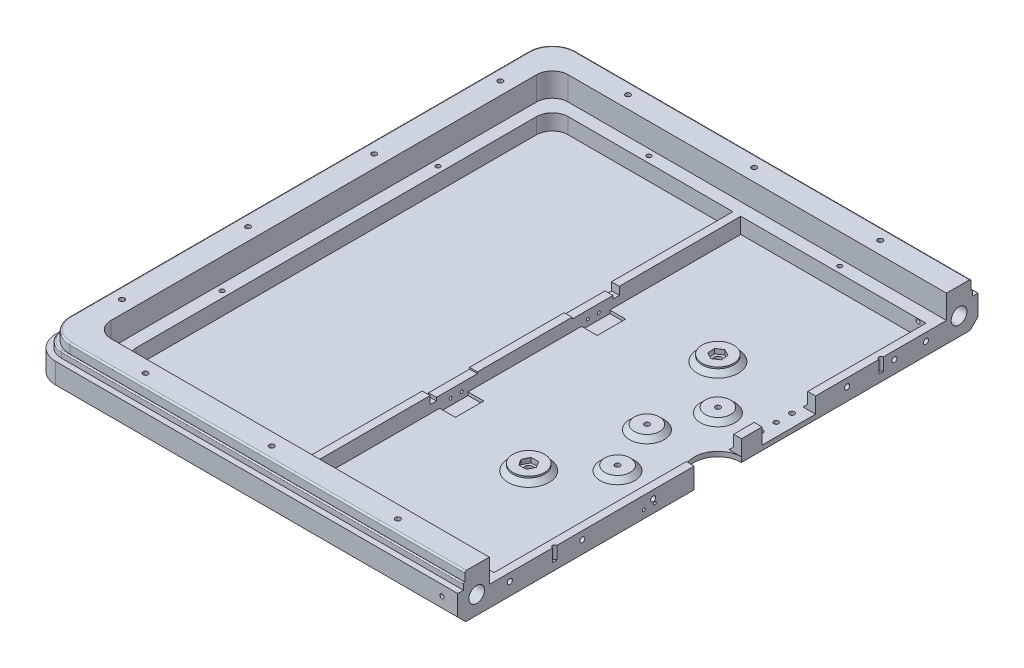
SolidWorks part; units mm, degrees
ref_plane "Front Plane" through (0, 0, 0) normal (0, 0, 1) x (1, 0, 0)
ref_plane "Top Plane" through (0, 0, 0) normal (0, 1, 0) x (1, 0, 0)
ref_plane "Right Plane" through (0, 0, 0) normal (1, 0, 0) x (0, 0, -1)
sketch "Sketch1" plane through (0, 0, 0) normal (0, 1, 0) x (1, 0, 0)
  line L1 (-270, -165) -> (270, -165)
  line L2 (-270, -165) -> (-270, 165)
  line L3 (-270, 165) -> (270, 165)
  line L4 (270, -165) -> (270, 165)
  line L5 (-270, -165) -> (270, 165) construction
  line L6 (-270, 165) -> (270, -165) construction
  point P0 (0, 0)
  dimension "D1" = 540
  dimension "D2" = 330
extrude "Boss-Extrude1" add sketch "Sketch1" along normal blind 3
sketch "Sketch2" plane through (0, 3, 0) normal (0, 1, 0) x (1, 0, 0)
  line L0 (250, 145) -> (-250, 145)
  line L1 (270, -165) -> (-270, -165)
  line L2 (270, -165) -> (270, 165)
  line L3 (270, 165) -> (-270, 165)
  line L4 (-270, -165) -> (-270, 165)
  line L5 (270, -165) -> (-270, 165) construction
  line L6 (270, 165) -> (-270, -165) construction
  line L7 (-250, -145) -> (-250, 145)
  line L8 (250, -145) -> (-250, -145)
  line L9 (250, -145) -> (250, 145)
  point P0 (0, 0)
  dimension "D1" = 20
  dimension "D2" = 540
extrude "Boss-Extrude2" add sketch "Sketch2" along normal blind 25 contours L0 L7 L8 L9 | L2 L1 L4 L3
fillet "Fillet1" radius 15 4 edges at (-270, 14, -165) (-270, 14, 165) (270, 14, 165) (270, 14, -165)
sketch "Sketch4" plane through (0, 28, 0) normal (0, 1, 0) x (1, 0, 0)
  line L0 (-270, 0) -> (-258, 0) construction
  line L1 (-270, -150) -> (-270, 150) construction
  line L2 (-258, 0) -> (-258, 40) construction
  line L3 (-258, 40) -> (-258, 120) construction
  line L4 (0, 0) -> (0, 145) construction
  line L5 (250, 145) -> (-250, 145) construction
  line L6 (0, 165) -> (0, 153) construction
  line L7 (255, 165) -> (-255, 165) construction
  line L8 (0, 153) -> (-50, 153) construction
  line L9 (-50, 153) -> (-130, 153) construction
  line L10 (-130, 153) -> (-210, 153) construction
  line L11 (130, 153) -> (210, 153) construction
  line L12 (50, 153) -> (130, 153) construction
  line L13 (258, 40) -> (258, 120) construction
  line L14 (0, 0) -> (78.1952, 0) construction
  line L15 (258, -40) -> (258, -120) construction
  line L16 (50, -153) -> (130, -153) construction
  line L17 (130, -153) -> (210, -153) construction
  line L18 (-130, -153) -> (-210, -153) construction
  line L19 (-50, -153) -> (-130, -153) construction
  line L20 (0, -153) -> (-50, -153) construction
  line L21 (0, -165) -> (0, -153) construction
  line L22 (-258, -40) -> (-258, -120) construction
  circle A0 centre (-258, 120) radius 1.6
  circle A1 centre (-258, 40) radius 1.6
  circle A2 centre (-210, 153) radius 1.6
  circle A3 centre (-130, 153) radius 1.6
  circle A4 centre (-50, 153) radius 1.6
  circle A5 centre (50, 153) radius 1.6
  circle A6 centre (130, 153) radius 1.6
  circle A7 centre (210, 153) radius 1.6
  circle A8 centre (258, 40) radius 1.6
  circle A9 centre (258, 120) radius 1.6
  circle A10 centre (258, -120) radius 1.6
  circle A11 centre (258, -40) radius 1.6
  circle A12 centre (210, -153) radius 1.6
  circle A13 centre (130, -153) radius 1.6
  circle A14 centre (50, -153) radius 1.6
  circle A15 centre (-50, -153) radius 1.6
  circle A16 centre (-130, -153) radius 1.6
  circle A17 centre (-210, -153) radius 1.6
  circle A18 centre (-258, -40) radius 1.6
  circle A19 centre (-258, -120) radius 1.6
  dimension "D1" = 50
  dimension "D2" = 80
  dimension "D3" = 80
  dimension "D4" = 12
  dimension "D5" = 12
  dimension "D6" = 40
  dimension "D7" = 80
extrude "Cut-Extrude1" cut sketch "Sketch4" against normal up to surface (28 mm away) up to face at (0, 0, 0)
sketch "Sketch5" plane through (0, 3, 0) normal (0, 1, 0) x (1, 0, 0)
  circle A0 centre (0, 0) radius 15
  dimension "D1" = 30
extrude "Cut-Extrude2" cut sketch "Sketch5" against normal up to surface (3 mm away) up to face at (-130, 0, 151.4)
chamfer "Chamfer1" distance 5 angle 45 8 edges at (270, 0, 0) (0, 0, -165) (0, 0, 165) (265.6066, 0, -160.6066) (265.6066, 0, 160.6066) (-265.6066, 0, -160.6066) (-265.6066, 0, 160.6066) (-270, 0, 0)
sketch "Sketch7" plane through (0, 0, 0) normal (0, -1, 0) x (1, 0, 0)
  line L1 (-60, -60) -> (60, -60) construction
  line L2 (-60, -60) -> (-60, 60) construction
  line L3 (-60, 60) -> (60, 60) construction
  line L4 (60, -60) -> (60, 60) construction
  line L5 (-60, -60) -> (60, 60) construction
  line L6 (-60, 60) -> (60, -60) construction
  circle A0 centre (-60, 60) radius 2.6
  circle A1 centre (60, 60) radius 2.6
  circle A2 centre (60, -60) radius 2.6
  circle A3 centre (-60, -60) radius 2.6
  point P0 (0, 0)
  dimension "D1" = 120
  dimension "D2" = 120
extrude "Cut-Extrude3" cut sketch "Sketch7" against normal up to surface (3 mm away) up to face at (0, 3, 15)
sketch "Sketch9" plane through (0, 0, 0) normal (0, -1, 0) x (1, 0, 0)
  line L0 (0, 0) -> (45, 0) construction
  line L1 (-31.8198, -31.8198) -> (31.8198, -31.8198) construction
  line L2 (-31.8198, -31.8198) -> (-31.8198, 31.8198) construction
  line L3 (-31.8198, 31.8198) -> (31.8198, 31.8198) construction
  line L4 (31.8198, -31.8198) -> (31.8198, 31.8198) construction
  line L5 (-31.8198, -31.8198) -> (31.8198, 31.8198) construction
  line L6 (-31.8198, 31.8198) -> (31.8198, -31.8198) construction
  line L7 (0, 0) -> (0, -31.8198) construction
  circle A0 centre (-31.8198, 31.8198) radius 1.6
  circle A1 centre (31.8198, 31.8198) radius 1.6
  circle A2 centre (31.8198, -31.8198) radius 1.6
  circle A3 centre (-31.8198, -31.8198) radius 1.6
  circle A4 centre (45, 0) radius 1.6
  circle A5 centre (-45, 0) radius 1.6
  point P0 (0, 0)
  dimension "D3" = 45
  dimension "D1" = 90
  dimension "D2" = 90
extrude "Cut-Extrude4" cut sketch "Sketch9" against normal blind 47
sketch "Sketch17" plane through (0, 28, 0) normal (0, 1, 0) x (1, 0, 0)
  line L0 (0, 0) -> (0, 165) construction
  line L1 (265, 165) -> (-265, 165) construction
sketch "Sketch18" plane through (0, 28, 0) normal (0, 1, 0) x (1, 0, 0)
  line L0 (0, 165) -> (0, -165) construction
  line L1 (265, 165) -> (-265, 165) construction
  line L2 (265, -165) -> (-265, -165) construction
sketch "Sketch19" plane through (0, 28, 0) normal (0, 1, 0) x (1, 0, 0)
  line L0 (250.5, 160.5) -> (-250.5, 160.5)
  line L1 (255, -165) -> (-255, -165)
  line L2 (270, -150) -> (270, 150)
  line L3 (255, 165) -> (-255, 165)
  line L4 (-270, -150) -> (-270, 150)
  line L5 (270, -165) -> (-270, 165) construction
  line L6 (270, 165) -> (-270, -165) construction
  line L7 (-265.5, -145.5) -> (-265.5, 145.5)
  line L8 (250.5, -160.5) -> (-250.5, -160.5)
  line L9 (265.5, -145.5) -> (265.5, 145.5)
  line L10 (255, 160.5) -> (-255, 160.5) construction
  line L11 (-265.5, -150) -> (-265.5, 150) construction
  line L12 (265.5, -150) -> (265.5, 150) construction
  line L13 (255, -160.5) -> (-255, -160.5) construction
  arc A0 (-270, -150) -> (-255, -165) centre (-255, -150) ccw
  arc A1 (255, -165) -> (270, -150) centre (255, -150) ccw
  arc A2 (270, 150) -> (255, 165) centre (255, 150) ccw
  arc A3 (-255, 165) -> (-270, 150) centre (-255, 150) ccw
  arc A4 (-255, 160.5) -> (-265.5, 150) centre (-255, 150) ccw construction
  arc A5 (-265.5, -150) -> (-255, -160.5) centre (-255, -150) ccw construction
  arc A6 (255, -160.5) -> (265.5, -150) centre (255, -150) ccw construction
  arc A7 (265.5, 150) -> (255, 160.5) centre (255, 150) ccw construction
  arc A8 (-250.5, 160.5) -> (-265.5, 145.5) centre (-250.5, 145.5) ccw
  arc A9 (265.5, 145.5) -> (250.5, 160.5) centre (250.5, 145.5) ccw
  arc A10 (265.5, -145.5) -> (250.5, -160.5) centre (250.5, -145.5) cw
  arc A11 (-250.5, -160.5) -> (-265.5, -145.5) centre (-250.5, -145.5) cw
  point P0 (0, 0)
  dimension "D3" = 15
  dimension "D5" = 15
  dimension "D6" = 15
  dimension "D7" = 15
  dimension "D8" = 15
  dimension "D1" = 330
  dimension "D2" = 540
  dimension "D4" = 4.5
extrude "Cut-Extrude5" cut sketch "Sketch19" against normal blind 10
fillet "Fillet2" radius 1 8 edges at (265.5, 28, 0) (0, 28, 160.5) (-265.5, 28, 0) (0, 28, -160.5) (261.1066, 28, -156.1066) (261.1066, 28, 156.1066) (-261.1066, 28, 156.1066) (-261.1066, 28, -156.1066)
sketch "Sketch20" plane through (0, 18, 0) normal (0, 1, 0) x (1, 0, 0)
  line L0 (0, 165) -> (0, -165) construction
  line L1 (-255, 165) -> (255, 165) construction
  line L2 (-270, 150) -> (-270, -150) construction
  line L3 (-255, -165) -> (255, -165) construction
  line L4 (270, 150) -> (270, -150) construction
  line L5 (-270, 165) -> (270, -165) construction
  line L6 (-270, -165) -> (270, 165) construction
  line L7 (-255, 161.4) -> (255, 161.4)
  line L8 (266.4, 150) -> (266.4, -150)
  line L9 (-255, -161.4) -> (255, -161.4)
  line L10 (-266.4, 150) -> (-266.4, -150)
  line L11 (-255, 157.9) -> (255, 157.9)
  line L12 (262.9, 150) -> (262.9, -150)
  line L13 (-255, -157.9) -> (255, -157.9)
  line L14 (-262.9, 150) -> (-262.9, -150)
  arc A0 (-270, -150) -> (-255, -165) centre (-255, -150) ccw construction
  arc A1 (270, -150) -> (255, -165) centre (255, -150) cw construction
  arc A2 (270, 150) -> (255, 165) centre (255, 150) ccw construction
  arc A3 (-255, 165) -> (-270, 150) centre (-255, 150) ccw construction
  arc A4 (266.4, 150) -> (255, 161.4) centre (255, 150) ccw
  arc A5 (266.4, -150) -> (255, -161.4) centre (255, -150) cw
  arc A6 (-266.4, -150) -> (-255, -161.4) centre (-255, -150) ccw
  arc A7 (-255, 161.4) -> (-266.4, 150) centre (-255, 150) ccw
  arc A8 (262.9, 150) -> (255, 157.9) centre (255, 150) ccw
  arc A9 (262.9, -150) -> (255, -157.9) centre (255, -150) cw
  arc A10 (-262.9, -150) -> (-255, -157.9) centre (-255, -150) ccw
  arc A11 (-255, 157.9) -> (-262.9, 150) centre (-255, 150) ccw
  point P0 (0, 0)
  dimension "D3" = 15
  dimension "D1" = 330
  dimension "D2" = 540
  dimension "D4" = 3.6
  dimension "D5" = 3.5
extrude "Boss-Extrude3" add sketch "Sketch20" along normal blind 4
fillet "Fillet4" radius 0.8 8 edges at (263.061, 22, -158.061) (266.4, 22, 0) (263.061, 22, 158.061) (0, 22, 161.4) (-263.061, 22, 158.061) (-266.4, 22, 0) (-263.061, 22, -158.061) (0, 22, -161.4)
sketch "Sketch23" plane through (0, 3, 0) normal (0, 1, 0) x (1, 0, 0)
  line L0 (250, 145) -> (-250, 145) construction
  line L1 (-5, -145) -> (5, -145)
  line L2 (-5, -145) -> (-5, 145)
  line L3 (-5, 145) -> (5, 145)
  line L4 (5, -145) -> (5, 145)
  line L5 (-5, -145) -> (5, 145) construction
  line L6 (-5, 145) -> (5, -145) construction
  line L7 (0, 0) -> (250, 0) construction
  line L8 (-5, -15) -> (5, -15)
  line L9 (-5, -15) -> (-5, 15)
  line L10 (-5, 15) -> (5, 15)
  line L11 (5, -15) -> (5, 15)
  line L12 (-5, -15) -> (5, 15) construction
  line L13 (-5, 15) -> (5, -15) construction
  line L14 (250, -145) -> (250, 145) construction
  line L15 (250, 145) -> (-250, 145) construction
  line L16 (122.5, -145) -> (127.5, -145)
  line L17 (122.5, -145) -> (122.5, 145)
  line L18 (122.5, 145) -> (127.5, 145)
  line L19 (127.5, -145) -> (127.5, 145)
  line L20 (122.5, -145) -> (127.5, 145) construction
  line L21 (122.5, 145) -> (127.5, -145) construction
  line L27 (0, 0) -> (0, 145) construction
  line L28 (-122.5, 145) -> (-127.5, 145)
  line L29 (-127.5, -145) -> (-127.5, 145)
  line L30 (-122.5, -145) -> (-127.5, -145)
  line L31 (-122.5, -145) -> (-122.5, 145)
  point P0 (0, 0)
  point P8 (0, 0)
  point P17 (125, 0)
  line M14 (-250, -145) -> (250, -145)
  line M16 (250, 145) -> (-250, 145)
  dimension "D1" = 30
  dimension "D2" = 10
  dimension "D3" = 5
extrude "Boss-Extrude4" add sketch "Sketch23" along normal blind 10 contours L2 L10 L4 M16 | L8 L2 L4 M14 | L17 L16 L19 L18 | L28 L29 L30 L31 region at (0, 3, 80) region at (0, 3, -80)
sketch "Sketch24" plane through (0, 3, 0) normal (0, 1, 0) x (1, 0, 0)
  line L0 (-242, 137) -> (242, 137)
  line L1 (-250, -145) -> (250, -145)
  line L2 (-250, -145) -> (-250, 145)
  line L3 (-250, 145) -> (250, 145)
  line L4 (250, -145) -> (250, 145)
  line L5 (-250, -145) -> (250, 145) construction
  line L6 (-250, 145) -> (250, -145) construction
  line L7 (242, -137) -> (242, 137)
  line L8 (-242, -137) -> (242, -137)
  line L9 (-242, -137) -> (-242, 137)
  point P0 (0, 0)
  dimension "D1" = 8
extrude "Boss-Extrude5" add sketch "Sketch24" along normal up to surface (10 mm away) up to face at (-125, 13, 0)
sketch "Sketch25" plane through (127.5, 0, 0) normal (1, 0, 0) x (0, 0, -1)
  line L0 (0, 5) -> (0, 13) construction
  line L1 (-150, 5) -> (150, 5) construction
  line L2 (-145, 13) -> (145, 13) construction
  line L3 (0, 13) -> (0, 5) construction
  line L4 (0, 5) -> (-40, 5) construction
  line L5 (-40, 5) -> (-47, 5) construction
  circle A0 centre (-47, 5) radius 0.9
  circle A1 centre (-40, 5) radius 0.9
  circle A2 centre (47, 5) radius 0.9
  circle A3 centre (40, 5) radius 0.9
  dimension "D1" = 8
  dimension "D2" = 40
  dimension "D3" = 7
extrude "Cut-Extrude6" cut sketch "Sketch25" against normal up to surface (255 mm away) up to face at (-127.5, 8, 0)
sketch "Sketch26" plane through (0, 3, 0) normal (0, 1, 0) x (1, 0, 0)
  line L0 (0, 0) -> (-122.5, 0) construction
  line L1 (-122.5, -137) -> (-122.5, 137) construction
  line L2 (-122.5, 0) -> (-122.5, 36) construction
  line L3 (-122.5, -137) -> (-122.5, 137) construction
  line L4 (-122.5, -54) -> (-112.5, -54)
  line L5 (-122.5, 36) -> (-112.5, 36)
  line L6 (-122.5, 36) -> (-122.5, 54)
  line L7 (-122.5, 54) -> (-112.5, 54)
  line L8 (-112.5, 36) -> (-112.5, 54)
  line L9 (-122.5, -36) -> (-112.5, -36)
  line L10 (-122.5, -36) -> (-122.5, -54)
  line L11 (-112.5, -36) -> (-112.5, -54)
  line L12 (0, 0) -> (0, 165) construction
  line L13 (122.5, -36) -> (122.5, -54)
  line L14 (122.5, -36) -> (112.5, -36)
  line L15 (112.5, -36) -> (112.5, -54)
  line L16 (122.5, -54) -> (112.5, -54)
  line L17 (122.5, 54) -> (112.5, 54)
  line L18 (112.5, 36) -> (112.5, 54)
  line L19 (122.5, 36) -> (112.5, 36)
  line L20 (122.5, 36) -> (122.5, 54)
  point P11 (-112.5, 45)
  dimension "D1" = 36
  dimension "D2" = 10
extrude "Cut-Extrude7" cut sketch "Sketch26" against normal blind 2
sketch "Sketch27" plane through (0, 13, 0) normal (0, 1, 0) x (1, 0, 0)
  line L0 (0, 0) -> (0, 165) construction
  line L1 (-122.5, 0) -> (-127.5, 0) construction
  line L2 (-122.5, -36) -> (-122.5, 36) construction
  line L3 (-127.5, -137) -> (-127.5, 137) construction
  line L4 (-127.5, -137) -> (-127.5, 137) construction
  line L5 (-122.5, -60) -> (-127.5, -60)
  line L6 (-122.5, -60) -> (-122.5, -30)
  line L7 (-122.5, 60) -> (-127.5, 60)
  line L8 (-127.5, -60) -> (-127.5, -30)
  line L9 (-122.5, -60) -> (-123.75, -30) construction
  line L10 (-122.5, 60) -> (-123.75, 30) construction
  line L11 (-127.5, 30) -> (-127.5, 60)
  line L12 (-127.5, -30) -> (-122.5, -30)
  line L14 (-127.5, 30) -> (-122.5, 30)
  line L16 (126.25, -30) -> (127.5, -60) construction
  line L17 (126.25, 30) -> (127.5, 60) construction
  line L18 (-126.25, 30) -> (-127.5, 60) construction
  line L19 (-126.25, -30) -> (-127.5, -60) construction
  line L20 (-122.5, 30) -> (-122.5, 60)
  line L21 (122.5, 60) -> (123.75, 30) construction
  line L22 (122.5, -60) -> (123.75, -30) construction
  line L23 (122.5, 0) -> (127.5, 0) construction
  line L24 (122.5, 30) -> (122.5, 60)
  line L25 (127.5, 30) -> (122.5, 30)
  line L26 (127.5, -30) -> (122.5, -30)
  line L27 (127.5, 30) -> (127.5, 60)
  line L28 (127.5, -60) -> (127.5, -30)
  line L29 (122.5, 60) -> (127.5, 60)
  line L30 (122.5, -60) -> (122.5, -30)
  line L31 (122.5, -60) -> (127.5, -60)
  point P10 (-125, 0)
  point P17 (-125, 0)
  point P40 (125, 0)
  dimension "D1" = 120
  dimension "D2" = 60
extrude "Cut-Extrude8" cut sketch "Sketch27" against normal blind 3
sketch "Sketch28" plane through (0, 13, 0) normal (0, 1, 0) x (1, 0, 0)
  line L1 (-127.5, 30) -> (-122.5, 30)
  line L2 (-127.5, 30) -> (-127.5, -30)
  line L3 (-127.5, -30) -> (-122.5, -30)
  line L4 (-122.5, 30) -> (-122.5, -30)
  line L5 (122.5, 30) -> (127.5, 30)
  line L6 (122.5, 30) -> (122.5, -30)
  line L7 (122.5, -30) -> (127.5, -30)
  line L8 (127.5, 30) -> (127.5, -30)
extrude "Cut-Extrude9" cut sketch "Sketch28" against normal blind 2
sketch "Sketch29" plane through (0, 10, 0) normal (0, 1, 0) x (1, 0, 0)
  line L0 (-122.5, 30) -> (-122.5, 60) construction
  line L1 (-127.5, 60) -> (-122.5, 60)
  line L2 (-127.5, 60) -> (-127.5, 56)
  line L3 (-127.5, 56) -> (-122.5, 56)
  line L4 (-122.5, 60) -> (-122.5, 56)
  line L5 (-122.5, -60) -> (-122.5, -30) construction
  line L6 (-127.5, -60) -> (-122.5, -60)
  line L7 (-127.5, -60) -> (-127.5, -56)
  line L8 (-127.5, -56) -> (-122.5, -56)
  line L9 (-122.5, -60) -> (-122.5, -56)
  line L10 (127.5, -60) -> (127.5, -30) construction
  line L11 (122.5, -60) -> (127.5, -60)
  line L12 (122.5, -60) -> (122.5, -56)
  line L13 (122.5, -56) -> (127.5, -56)
  line L14 (127.5, -60) -> (127.5, -56)
  line L15 (127.5, -137) -> (127.5, 137) construction
  line L16 (122.5, 60) -> (127.5, 60)
  line L17 (122.5, 60) -> (122.5, 56)
  line L18 (122.5, 56) -> (127.5, 56)
  line L19 (127.5, 60) -> (127.5, 56)
extrude "Cut-Extrude10" cut sketch "Sketch29" against normal blind 2
sketch "Sketch31" plane through (0, 13, 0) normal (0, 1, 0) x (1, 0, 0)
  line L0 (0, 165) -> (0, 45) construction
  line L1 (255, 165) -> (-255, 165) construction
  line L3 (-8, 62) -> (8, 62)
  line L4 (-8, 62) -> (-8, 28)
  line L5 (-8, 28) -> (8, 28)
  line L6 (8, 62) -> (8, 28)
  line L7 (-8, 62) -> (8, 28) construction
  line L8 (-8, 28) -> (8, 62) construction
  point P11 (0, 0)
  point P12 (0, 0)
  dimension "D1" = 120
  dimension "D2" = 34
  dimension "D3" = 16
  dimension "D4" = 16
sketch "Sketch32" plane through (-270, 0, 0) normal (-1, 0, 0) x (0, 0, 1)
  line L0 (-30, 13) -> (-30, 18) construction
  line L1 (-62, 13) -> (-28, 13) construction
  line L2 (-150, 18) -> (150, 18) construction
  line L3 (-30, 18) -> (-30, 51) construction
extrude "Boss-Extrude6" add sketch "Sketch31" along normal blind 53 and the other way up to surface (10 mm away) other way up to face at (-60, 3, 57.4)
fillet "Fillet5" radius 15 2 edges at (0, 66, -28) (0, 66, -62)
sketch "Sketch34" plane through (-8, 0, 0) normal (-1, 0, 0) x (0, 0, 1)
  line L0 (-165, 18) -> (-45, 18) construction
  line L1 (-150, 18) -> (150, 18) construction
  line L2 (-45, 18) -> (-45, 53) construction
  circle A0 centre (-45, 53) radius 3
  dimension "D3" = 6
  dimension "D1" = 120
  dimension "D2" = 35
extrude "Cut-Extrude11" cut sketch "Sketch34" against normal blind 53
sketch "Sketch35" plane through (0, 3, 0) normal (0, 1, 0) x (1, 0, 0)
  circle A0 centre (-31.8198, 31.8198) radius 1.6
  circle A1 centre (-31.8198, 31.8198) radius 8
  circle A2 centre (31.8198, 31.8198) radius 1.6
  circle A3 centre (31.8198, 31.8198) radius 8
  circle A4 centre (31.8198, -31.8198) radius 1.6
  circle A5 centre (31.8198, -31.8198) radius 8
  circle A6 centre (-31.8198, -31.8198) radius 1.6
  circle A7 centre (-31.8198, -31.8198) radius 8
  circle A8 centre (-45, 0) radius 8
  circle A9 centre (45, 0) radius 8
  circle A10 centre (45, 0) radius 1.6
  circle A11 centre (-45, 0) radius 1.6
  point P16 (0, 0)
  dimension "D1" = 16
  dimension "D2" = 3.2
  dimension "D3" = 4
extrude "Boss-Extrude7" add sketch "Sketch35" along normal blind 3
chamfer "Chamfer2" distance 3 angle 45 6 edges at (31.8198, 3, 23.8198) (-31.8198, 3, 23.8198) (-31.8198, 3, -39.8198) (31.8198, 3, -39.8198) (45, 3, -8) (-45, 3, -8)
sketch "Sketch37" plane through (0, 66, 0) normal (0, 1, 0) x (1, 0, 0)
  line L0 (0, 47) -> (0, 43) construction
  line L1 (8, 47) -> (-8, 47) construction
  line L2 (-8, 43) -> (8, 43) construction
  line L4 (-8, 28) -> (8, 28)
  line L5 (-8, 28) -> (-8, 62)
  line L6 (-8, 62) -> (8, 62)
  line L7 (8, 28) -> (8, 62)
  line L8 (-8, 28) -> (8, 62) construction
  line L9 (-8, 62) -> (8, 28) construction
  point P6 (0, 45)
extrude "Cut-Extrude12" cut sketch "Sketch37" against normal up to surface (63 mm away) up to face at (-45, 3, -11)
sketch "Sketch38" plane through (0, 3, 0) normal (0, 1, 0) x (1, 0, 0)
  line L0 (0, 62) -> (0, 28) construction
  line L1 (5, 62) -> (-5, 62) construction
  line L2 (-5, 28) -> (5, 28) construction
  line L3 (0, 28) -> (0, 45) construction
  line L4 (0, 45) -> (8, 45) construction
  line L5 (8, 45) -> (8, 55) construction
  circle A0 centre (8, 55) radius 1.6
  circle A1 centre (8, 35) radius 1.6
  circle A2 centre (-8, 35) radius 1.6
  circle A3 centre (-8, 55) radius 1.6
  circle A4 centre (8, 45) radius 1.5
  circle A5 centre (-8, 45) radius 1.5
  dimension "D2" = 10
  dimension "D1" = 8
extrude "Cut-Extrude13" cut sketch "Sketch38" against normal blind 90
chamfer "Chamfer3" distance 3 angle 45 6 edges at (-5, 3, 76) (-5, 3, -21.5) (5, 3, -21.5) (5, 3, 76) (5, 3, -99.5) (-5, 3, -99.5)
sketch "Sketch39" plane through (0, 13, 0) normal (0, 1, 0) x (1, 0, 0)
  line L0 (-242, 0) -> (-242, 137) construction
  line L1 (-242, 137) -> (-242, -137) construction
  line L2 (-242, 137) -> (-242, 68.5) construction
  line L3 (-242, 68.5) -> (-250, 68.5) construction
  line L4 (-250, -145) -> (-250, 145) construction
  line L5 (-184.75, 137) -> (-184.75, 145) construction
  line L6 (-127.5, 137) -> (-242, 137) construction
  line L7 (250, 145) -> (-250, 145) construction
  line L8 (-63.75, 137) -> (-63.75, 145) construction
  line L10 (-5, 137) -> (-122.5, 137) construction
  line L11 (250, 145) -> (-250, 145) construction
  line L12 (0, 0) -> (0, 145) construction
  line L13 (63.75, 137) -> (63.75, 145) construction
  line L14 (184.75, 137) -> (184.75, 145) construction
  line L15 (242, 68.5) -> (250, 68.5) construction
  line L16 (242, 137) -> (242, 68.5) construction
  line L17 (0, 62) -> (0, 145) construction
  line L18 (5, 62) -> (-5, 62) construction
  line L19 (0, 0) -> (250, 0) construction
  line L20 (250, -145) -> (250, 145) construction
  line L21 (0, -62) -> (0, -145) construction
  line L22 (242, -137) -> (242, -68.5) construction
  line L23 (242, -68.5) -> (250, -68.5) construction
  line L24 (184.75, -137) -> (184.75, -145) construction
  line L25 (63.75, -137) -> (63.75, -145) construction
  line L26 (-63.75, -137) -> (-63.75, -145) construction
  line L27 (-184.75, -137) -> (-184.75, -145) construction
  line L28 (-242, -68.5) -> (-250, -68.5) construction
  line L29 (-242, -137) -> (-242, -68.5) construction
  circle A0 centre (-246, 68.5) radius 1.4
  circle A1 centre (-184.75, 141) radius 1.4
  circle A2 centre (-63.75, 141) radius 1.4
  circle A3 centre (63.75, 141) radius 1.4
  circle A4 centre (184.75, 141) radius 1.4
  circle A5 centre (246, 68.5) radius 1.4
  circle A6 centre (0, 103.5) radius 1.4
  circle A7 centre (0, -103.5) radius 1.4
  circle A8 centre (246, -68.5) radius 1.4
  circle A9 centre (184.75, -141) radius 1.4
  circle A10 centre (63.75, -141) radius 1.4
  circle A11 centre (-63.75, -141) radius 1.4
  circle A12 centre (-184.75, -141) radius 1.4
  circle A13 centre (-246, -68.5) radius 1.4
extrude "Cut-Extrude14" cut sketch "Sketch39" against normal blind 8
fillet "Fillet6" radius 10 4 edges at (-242, 8, -137) (-242, 8, 137) (242, 8, 137) (242, 8, -137)
fillet "Fillet7" radius 10 4 edges at (250, 20.5, 145) (250, 20.5, -145) (-250, 20.5, 145) (-250, 20.5, -145)
sketch "Sketch41" plane through (0, 0, 0) normal (1, 0, 0) x (0, 0, -1)
  line L0 (165, 11.5) -> (153, 11.5) construction
  line L1 (165, 18) -> (165, 5) construction
  line L2 (0, 0) -> (0, 98.4706) construction
  circle A0 centre (153, 11.5) radius 5
  circle A1 centre (-153, 11.5) radius 5
  dimension "D1" = 12
extrude "Cut-Extrude15" cut sketch "Sketch41" against normal blind 30 and the other way blind 30
sketch "Sketch42" plane through (5, 0, 0) normal (1, 0, 0) x (0, 0, -1)
  line L0 (-132, 3) -> (-132, 13) construction
  line L1 (-127, 3) -> (-137, 3) construction
  line L2 (-135, 13) -> (135, 13) construction
  line L3 (-102.1, 13) -> (-69.9, 13) construction
  line L4 (-69.9, 13) -> (-86, 13) construction
  line L5 (-86, 13) -> (-86, 3) construction
  line L6 (-127, 3) -> (127, 3) construction
  line L7 (-67.1, 13) -> (-15, 13) construction
  line L8 (-15, 13) -> (-41.05, 13) construction
  line L9 (-41.05, 13) -> (-41.05, 3) construction
  line L10 (145, 13) -> (145, 3) construction
  line L11 (145, 3) -> (145, 8) construction
  line L12 (145, 8) -> (132, 8) construction
  line L13 (132, 8) -> (112, 8) construction
  line L14 (112, 8) -> (82, 8) construction
  circle A0 centre (112, 8) radius 1.6
  circle A1 centre (132, 8) radius 1.6
  circle A2 centre (82, 8) radius 1.6
  circle A3 centre (-86, 8) radius 1.6
  circle A4 centre (-132, 8) radius 1.6
  circle A5 centre (-41.05, 8) radius 1.6
  dimension "D1" = 30
  dimension "D2" = 20
  dimension "D3" = 13
extrude "Cut-Extrude16" cut sketch "Sketch42" against normal blind 30 and the other way blind 10
sketch "Sketch43" plane through (5, 0, 0) normal (1, 0, 0) x (0, 0, -1)
  line L0 (-87.6166, 10.8) -> (-89.2332, 8)
  line L1 (-128.7668, 8) -> (-130.3834, 10.8)
  line L2 (-130.3834, 10.8) -> (-133.6166, 10.8)
  line L3 (-133.6166, 10.8) -> (-135.2332, 8)
  line L4 (-135.2332, 8) -> (-133.6166, 5.2)
  line L5 (-133.6166, 5.2) -> (-130.3834, 5.2)
  line L6 (-130.3834, 5.2) -> (-128.7668, 8)
  line L7 (-89.2332, 8) -> (-87.6166, 5.2)
  line L8 (-87.6166, 5.2) -> (-84.3834, 5.2)
  line L9 (-82.7668, 8) -> (-84.3834, 10.8)
  line L10 (-84.3834, 10.8) -> (-87.6166, 10.8)
  line L11 (-84.3834, 5.2) -> (-82.7668, 8)
  line L12 (-37.8168, 8) -> (-39.4334, 10.8)
  line L13 (-39.4334, 5.2) -> (-37.8168, 8)
  line L14 (-42.6666, 10.8) -> (-44.2832, 8)
  line L15 (-39.4334, 10.8) -> (-42.6666, 10.8)
  line L16 (-42.6666, 5.2) -> (-39.4334, 5.2)
  line L17 (-44.2832, 8) -> (-42.6666, 5.2)
  line L18 (85.2332, 8) -> (83.6166, 10.8)
  line L19 (83.6166, 5.2) -> (85.2332, 8)
  line L20 (80.3834, 10.8) -> (78.7668, 8)
  line L21 (83.6166, 10.8) -> (80.3834, 10.8)
  line L22 (80.3834, 5.2) -> (83.6166, 5.2)
  line L23 (78.7668, 8) -> (80.3834, 5.2)
  line L24 (115.2332, 8) -> (113.6166, 10.8)
  line L25 (113.6166, 5.2) -> (115.2332, 8)
  line L26 (110.3834, 10.8) -> (108.7668, 8)
  line L27 (113.6166, 10.8) -> (110.3834, 10.8)
  line L28 (110.3834, 5.2) -> (113.6166, 5.2)
  line L29 (108.7668, 8) -> (110.3834, 5.2)
  line L30 (82, 8) -> (112, 8) construction
  line L31 (112, 8) -> (132, 8) construction
  line L32 (130.3834, 10.8) -> (128.7668, 8)
  line L33 (130.3834, 5.2) -> (133.6166, 5.2)
  line L34 (135.2332, 8) -> (133.6166, 10.8)
  line L35 (133.6166, 10.8) -> (130.3834, 10.8)
  line L36 (128.7668, 8) -> (130.3834, 5.2)
  line L37 (133.6166, 5.2) -> (135.2332, 8)
  circle A0 centre (-132, 8) radius 2.8 construction
  circle A1 centre (-86, 8) radius 2.8 construction
  circle A2 centre (-41.05, 8) radius 2.8 construction
  circle A3 centre (82, 8) radius 2.8 construction
  circle A4 centre (112, 8) radius 2.8 construction
  circle A5 centre (132, 8) radius 2.8 construction
  dimension "D1" = 5.6
extrude "Cut-Extrude17" cut sketch "Sketch43" against normal blind 2 and the other way blind 17
sketch "Sketch45" plane through (0, 3, 0) normal (0, 1, 0) x (1, 0, 0)
  circle A0 centre (-60, 60) radius 10
  circle A1 centre (-60, 60) radius 2.6
  circle A2 centre (60, 60) radius 10
  circle A3 centre (60, 60) radius 2.6
  circle A4 centre (60, -60) radius 10
  circle A5 centre (60, -60) radius 2.6
  circle A6 centre (-60, -60) radius 10
  circle A7 centre (-60, -60) radius 2.6
  point P16 (0, 0)
  dimension "D1" = 20
  dimension "D2" = 4
extrude "Boss-Extrude8" add sketch "Sketch45" along normal blind 4
chamfer "Chamfer4" distance 3 angle 45 4 edges at (-60, 3, -70) (60, 3, -70) (-60, 3, 50) (60, 3, 50)
sketch "Sketch48" plane through (0, 7, 0) normal (0, 1, 0) x (1, 0, 0)
  line L0 (62.567, 56.091) -> (64.6688, 60.2686)
  line L1 (-56.091, 62.567) -> (-60.2686, 64.6688)
  line L2 (-60.2686, 64.6688) -> (-64.1776, 62.1018)
  line L3 (-64.1776, 62.1018) -> (-63.909, 57.433)
  line L4 (-63.909, 57.433) -> (-59.7314, 55.3312)
  line L5 (-59.7314, 55.3312) -> (-55.8224, 57.8982)
  line L6 (-55.8224, 57.8982) -> (-56.091, 62.567)
  line L7 (64.6688, 60.2686) -> (62.1018, 64.1776)
  line L8 (62.1018, 64.1776) -> (57.433, 63.909)
  line L9 (57.433, 63.909) -> (55.3312, 59.7314)
  line L10 (55.3312, 59.7314) -> (57.8982, 55.8224)
  line L11 (57.8982, 55.8224) -> (62.567, 56.091)
  line L12 (56.091, -62.567) -> (60.2686, -64.6688)
  line L13 (60.2686, -64.6688) -> (64.1776, -62.1018)
  line L14 (64.1776, -62.1018) -> (63.909, -57.433)
  line L15 (63.909, -57.433) -> (59.7314, -55.3312)
  line L16 (59.7314, -55.3312) -> (55.8224, -57.8982)
  line L17 (55.8224, -57.8982) -> (56.091, -62.567)
  line L18 (-62.567, -56.091) -> (-64.6688, -60.2686)
  line L19 (-64.6688, -60.2686) -> (-62.1018, -64.1776)
  line L20 (-62.1018, -64.1776) -> (-57.433, -63.909)
  line L21 (-57.433, -63.909) -> (-55.3312, -59.7314)
  line L22 (-55.3312, -59.7314) -> (-57.8982, -55.8224)
  line L23 (-57.8982, -55.8224) -> (-62.567, -56.091)
  circle A0 centre (-60, 60) radius 4.05 construction
  circle A1 centre (60, 60) radius 4.05 construction
  circle A2 centre (60, -60) radius 4.05 construction
  circle A3 centre (-60, -60) radius 4.05 construction
  point P36 (0, 0)
  dimension "D1" = 8.1
  dimension "D2" = 4
extrude "Cut-Extrude18" cut sketch "Sketch48" against normal blind 3
sketch "Sketch49" plane through (0, 0, 0) normal (0, -1, 0) x (1, 0, 0)
  circle A0 centre (0, 0) radius 60
sketch "Sketch50" plane through (0, 0, 0) normal (0, -1, 0) x (1, 0, 0)
  line L1 (-60, 60) -> (60, 60) construction
sketch "Sketch52" plane through (0, 0, 165) normal (0, 0, 1) x (1, 0, 0)
  line L0 (0, 5) -> (0, 18) construction
  line L1 (-255, 5) -> (255, 5) construction
  line L2 (-255, 18) -> (255, 18) construction
  line L3 (0, 18) -> (0, 11.5) construction
  line L4 (0, 11.5) -> (-10, 11.5) construction
  circle A0 centre (-10, 11.5) radius 1.35
  circle A1 centre (10, 11.5) radius 1.35
  dimension "D2" = 2.7
  dimension "D1" = 10
extrude "Cut-Extrude20" cut sketch "Sketch52" against normal up to surface (330 mm away) contours A0 | A1 region at (-10, 11.5, 165) up to face at (0, 11.5, -165)
sketch "Sketch51" plane through (0, 28, 0) normal (0, 1, 0) x (1, 0, 0)
  line L0 (0, 0) -> (0, 165) construction
  line L1 (255, 165) -> (-255, 165) construction
  line L3 (0, 165) -> (369.7515, 165)
  line L4 (0, 165) -> (0, -203.5915)
  line L5 (0, -203.5915) -> (369.7515, -203.5915)
  line L6 (369.7515, 165) -> (369.7515, -203.5915)
extrude "Cut-Extrude21" cut sketch "Sketch51" against normal up to surface (28 mm away) up to face at (8, 0, -36.6)
